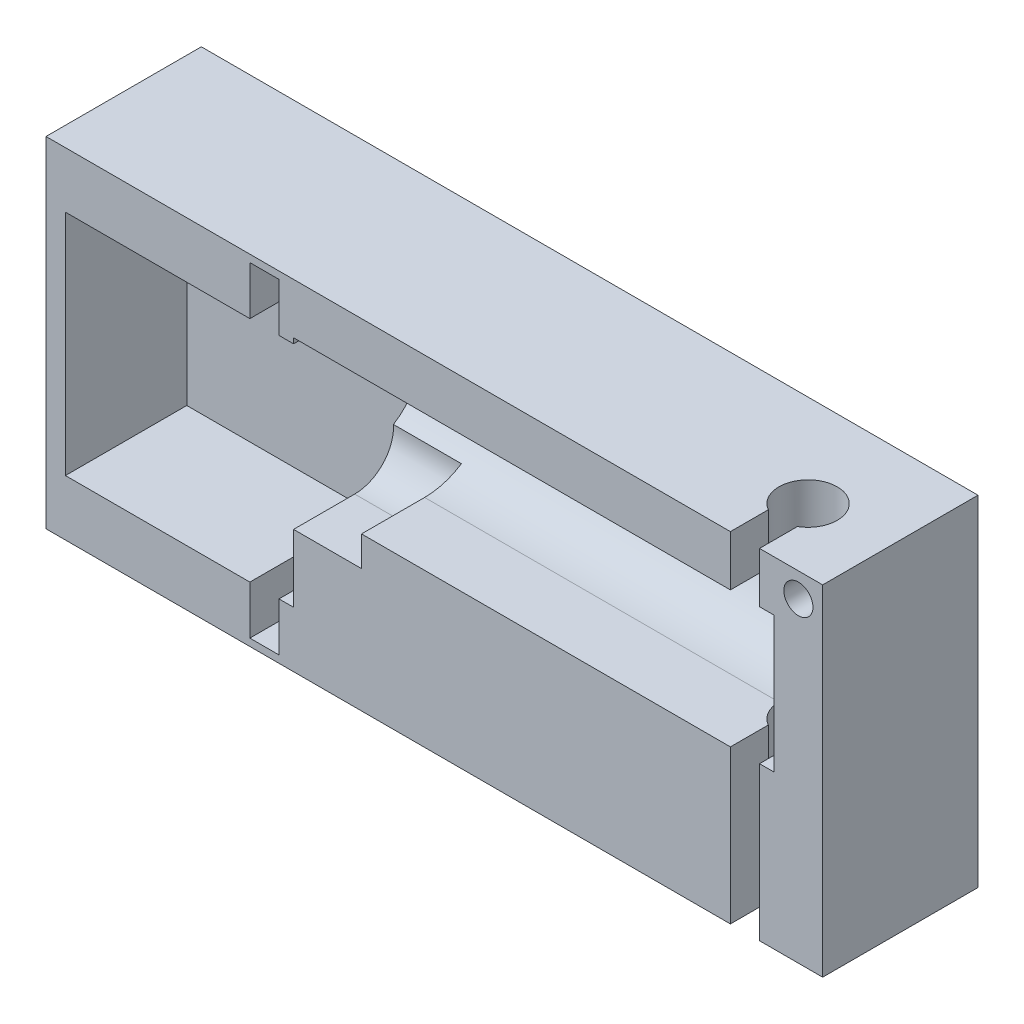
SolidWorks part; units mm, degrees
ref_plane "Front Plane" through (0, 0, 0) normal (0, 0, 1) x (1, 0, 0)
ref_plane "Top Plane" through (0, 0, 0) normal (0, 1, 0) x (1, 0, 0)
ref_plane "Right Plane" through (0, 0, 0) normal (1, 0, 0) x (0, 0, -1)
sketch "Sketch1" plane through (0, 0, 0) normal (0, 0, 1) x (1, 0, 0)
  line L0 (8.7404, -4.0789) -> (8.7404, 4.0789)
  line L1 (-37.5, 17.5) -> (37.5, 17.5)
  line L2 (-37.5, 17.5) -> (-37.5, -17.5)
  line L3 (-37.5, -17.5) -> (37.5, -17.5)
  line L4 (37.5, 17.5) -> (37.5, -17.5)
  line L5 (-37.5, 17.5) -> (37.5, -17.5) construction
  line L6 (-37.5, -17.5) -> (37.5, 17.5) construction
  line L10 (10.2694, 4.7924) -> (10.2694, -4.7924)
  point P0 (0, 0)
  dimension "D1" = 35
  dimension "D2" = 75
extrude "Boss-Extrude5" add sketch "Sketch1" along normal blind 16 contours L4 L1 L2 L3 region at (0, 0, 0)
sketch "Sketch2" plane through (0, 0, 16) normal (0, 0, 1) x (1, 0, 0)
  line L0 (-37.5, 17.5) -> (-37.5, -17.5) construction
  line L1 (-35.5, 11.75) -> (-16.5, 11.75)
  line L2 (-35.5, 11.75) -> (-35.5, -11.75)
  line L3 (-35.5, -11.75) -> (-16.5, -11.75)
  line L4 (-12, 11.75) -> (-12, -11.75)
  line L5 (-37.5, -17.5) -> (37.5, -17.5) construction
  line L7 (-13.5, -11.75) -> (-13.5, -16.75)
  line L8 (-16.5, 16.75) -> (-13.5, 16.75)
  line L9 (-16.5, 16.75) -> (-16.5, 11.75)
  line L10 (-16.5, -16.75) -> (-13.5, -16.75)
  line L11 (-13.5, 16.75) -> (-13.5, 11.75)
  line L12 (-16.5, -11.75) -> (-16.5, -16.75)
  line L13 (-13.5, -11.75) -> (-12, -11.75)
  line L14 (-13.5, 11.75) -> (-12, 11.75)
  dimension "D1" = 23.5
  dimension "D2" = 23.5
  dimension "D3" = 2
  dimension "D4" = 5.75
  dimension "D5" = 3
  dimension "D6" = 5
  dimension "D7" = 5
  dimension "D8" = 19
extrude "Cut-Extrude1" cut sketch "Sketch2" against normal blind 12.5 contours L1 L9 L8 L11 L14 L4 L13 L7 L10 L12 L3 L2
sketch "Sketch3" plane through (-12, 0, 0) normal (-1, 0, 0) x (0, 0, 1)
  line L0 (9.5, 12.2967) -> (16, 12.2967)
  line L1 (16, 12.2967) -> (16, -1.7033)
  line L2 (16, 11.75) -> (16, -11.75) construction
  line L3 (16, -1.7033) -> (9.5, -1.7033)
  arc A0 (9.5, 12.2967) -> (9.5, -1.7033) centre (9.5, 5.2967) ccw
  point P2 (0, 0)
  point P5 (9.5, 5.2967)
  point P6 (9.5, 5.2967)
  point P7 (9.5, 5.2967)
  point P8 (0, 0)
  point P10 (9.5, 5)
  point P11 (7.9232, 4.9712)
  point P12 (9.5, 5.2967)
  point P13 (9.5, 5.2967)
  point P14 (0, 0)
  point P15 (0, 0)
  point P17 (9.5, 5.2967)
  point P18 (9.5, 5.2967)
  point P19 (9.5, 5.2967)
  point P21 (0, 0)
  point P22 (0, 0)
  point P23 (0, 0)
  point P24 (0, 0)
  dimension "D1" = 7
extrude "Cut-Extrude2" cut sketch "Sketch3" against normal up to next
sketch "Sketch5" plane through (-12, 0, 0) normal (-1, 0, 0) x (0, 0, 1)
  line L0 (9.702, -4.8) -> (16, -4.8)
  line L1 (16, 17.5) -> (16, -17.5) construction
  line L2 (16, -4.8) -> (16, 3.2)
  line L3 (16, 12.2967) -> (16, -1.7033) construction
  line L4 (16, 3.2) -> (9.702, 3.2)
  arc A0 (9.702, 3.2) -> (9.702, -4.8) centre (9.702, -0.8) ccw
  dimension "D1" = 8
  dimension "D2" = 6.1
extrude "Cut-Extrude3" cut sketch "Sketch5" against normal blind 7
sketch "Sketch6" plane through (37.5, 0, 0) normal (1, 0, 0) x (0, 0, -1)
  line L1 (-16, -17.5) -> (0, -17.5)
  line L2 (-16, -17.5) -> (-16, 17.5)
  line L3 (-16, 17.5) -> (0, 17.5)
  line L4 (0, -17.5) -> (0, 17.5)
extrude "Boss-Extrude6" add sketch "Sketch6" along normal blind 5
sketch "Sketch7" plane through (0, -17.5, 0) normal (0, -1, 0) x (1, 0, 0)
  line L0 (34.4967, 9.5) -> (34.4967, 16) construction
  line L1 (37.5, 9.5) -> (-5, 9.5) construction
  line L3 (32.9967, 12.0981) -> (32.9967, 16)
  line L7 (32.9967, 16) -> (35.9967, 16)
  line L8 (35.9967, 16) -> (35.9967, 12.0981)
  line L9 (32.9967, 12.0981) -> (34.4967, 9.5) construction
  line L10 (34.4967, 9.5) -> (35.9967, 12.0981) construction
  arc A1 (35.9967, 12.0981) -> (32.9967, 12.0981) centre (34.4967, 9.5) cw
  point P1 (0, 0)
  dimension "D1" = 30
  dimension "D2" = 3
extrude "Cut-Extrude4" cut sketch "Sketch7" against normal through all
sketch "Sketch8" plane through (0, 0, 16) normal (0, 0, 1) x (1, 0, 0)
  circle A0 centre (40, 15) radius 1.5
  dimension "D1" = 3
extrude "Cut-Extrude5" cut sketch "Sketch8" against normal blind 13
